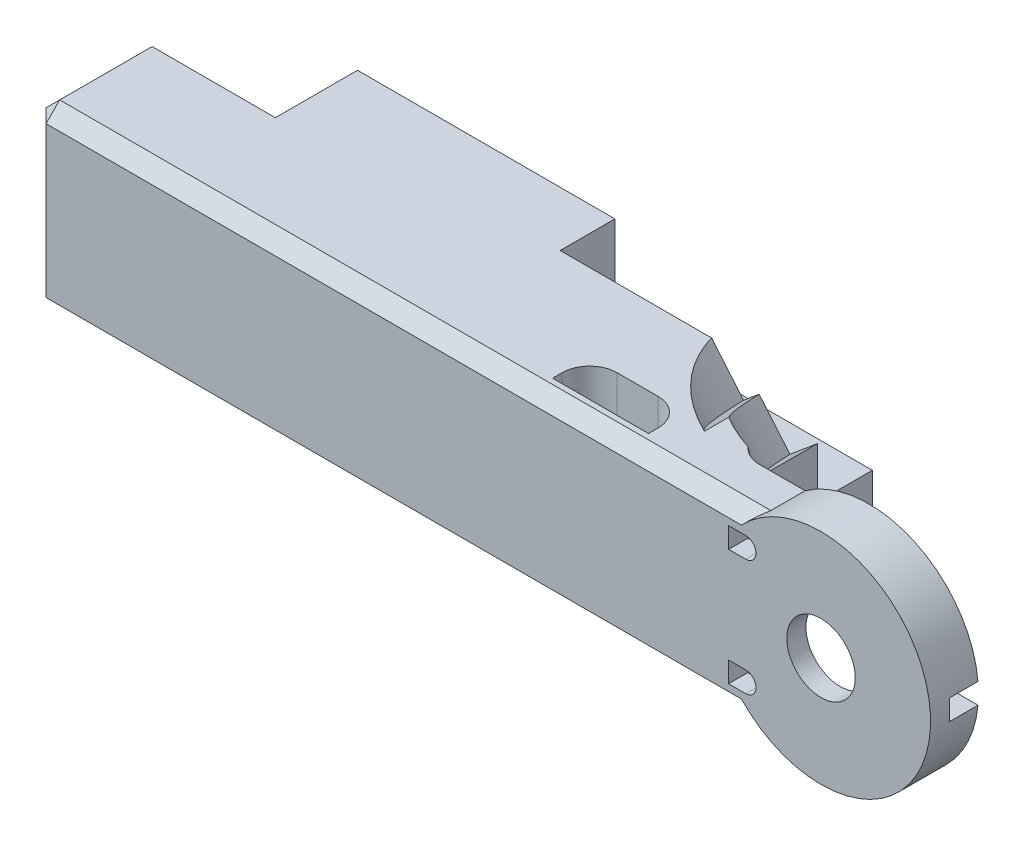
SolidWorks part; units mm, degrees
ref_plane "Front Plane" through (0, 0, 0) normal (0, 0, 1) x (1, 0, 0)
ref_plane "Top Plane" through (0, 0, 0) normal (0, 1, 0) x (1, 0, 0)
ref_plane "Right Plane" through (0, 0, 0) normal (1, 0, 0) x (0, 0, -1)
sketch "Sketch1" plane through (0, 0, 0) normal (0, 0, 1) x (1, 0, 0)
  line L0 (-1000, 0) -> (49000, 0) construction
  line L1 (-1003.2111, 6.5) -> (48996.7889, 6.5) construction
  line L2 (-1004.8419, -6.5) -> (48995.1581, -6.5) construction
  line L3 (-15, -6.5) -> (-15, 6.5)
  line L4 (-15, 6.5) -> (-4.6637, 6.5)
  line L5 (-15, -6.5) -> (-4.6637, -6.5)
  arc A0 (-4.6637, -6.5) -> (-4.6637, 6.5) centre (0, 0) ccw
  arc A1 (-8, 0) -> (-4.6637, -6.5) centre (0, 0) ccw construction
  arc A2 (-4.6637, 6.5) -> (-8, 0) centre (0, 0) ccw construction
  point P12 (-15, 0)
  dimension "D1" = 16
  dimension "D2" = 13
  dimension "D3" = 15
extrude "Boss-Extrude1" add sketch "Sketch1" along normal blind 3.5
sketch "Sketch2" plane through (0, 0, 0) normal (0, 0, -1) x (-1, 0, 0)
  line L0 (-1000, 0) -> (49000, 0) construction
  line L1 (0, -1000) -> (0, 49000) construction
  line L3 (-5.75, -1008.4841) -> (-5.75, -0.75) construction
  line L4 (-998.5902, -5.75) -> (49001.4098, -5.75) construction
  line L5 (-997.2865, 5.75) -> (49002.7135, 5.75) construction
  line L6 (-5.75, -0.75) -> (-7.9648, -0.75)
  line L7 (-5.75, 0.75) -> (-7.9648, 0.75)
  line L8 (-5.75, -2.5) -> (-5.75, -0.75)
  line L9 (-5.75, -2.5) -> (-2.5, -5.75)
  line L10 (-5.75, 2.5) -> (-2.5, 5.75)
  line L11 (-2.5, -5.75) -> (6.75, -5.75)
  line L12 (-2.5, 5.75) -> (6.75, 5.75)
  line L13 (6.75, -1004.2518) -> (6.75, 48995.7482) construction
  line L15 (6.75, -5.75) -> (6.75, 5.75)
  line L16 (-5.75, 0) -> (-5.75, 0.75) construction
  line L17 (-5.75, 0.75) -> (-5.75, 2.5)
  line L18 (-5.75, 0) -> (-5.75, 0.75) construction
  line L19 (-5.75, 0.75) -> (-5.75, 48991.5159) construction
  line L20 (-5.75, -0.75) -> (-5.75, 0) construction
  line L21 (-5.75, -0.75) -> (-5.75, 0) construction
  line L22 (-2.5, -1002.5522) -> (-2.5, 48997.4478) construction
  arc A0 (-7.9648, -0.75) -> (-7.9648, 0.75) centre (0, 0) cw
  circle A1 centre (0, 0) radius 8 construction
  point P25 (-5.5, 0)
  dimension "D6" = 8
  dimension "D1" = 5.75
  dimension "D2" = 5.75
  dimension "D3" = 5.75
  dimension "D4" = 0.75
  dimension "D5" = 0.75
  dimension "D7" = 5
  dimension "D8" = 45
  dimension "D9" = 45
  dimension "D10" = 2.5
  dimension "D11" = 6.75
extrude "Cut-Extrude1" cut sketch "Sketch2" against normal blind 2.1
sketch "Sketch3" plane through (0, 0, 2.1) normal (0, 0, -1) x (-1, 0, 0)
  line L0 (5.5, -5) -> (6.75, -5)
  line L1 (5.5, -3.5) -> (6.75, -3.5)
  line L2 (5.5, 3.5) -> (6.75, 3.5)
  line L3 (5.5, 5) -> (6.75, 5)
  line L5 (6.75, -5.75) -> (6.75, 5.75) construction
  line L7 (6.75, 5) -> (6.75, 3.5)
  line L9 (6.75, -3.5) -> (6.75, -5)
  circle A0 centre (0, 0) radius 2.5
  arc A1 (5.5, -3.5) -> (5.5, -5) centre (5.5, -4.25) ccw
  arc A2 (5.5, 5) -> (5.5, 3.5) centre (5.5, 4.25) ccw
  arc A6 (5.5, -5) -> (5.5, -3.5) centre (5.5, -4.25) ccw construction
  arc A7 (5.5, 3.5) -> (5.5, 5) centre (5.5, 4.25) ccw construction
  dimension "D1" = 5
  dimension "D2" = 1.5
  dimension "D3" = 1.5
extrude "Cut-Extrude2" cut sketch "Sketch3" against normal through all
sketch "Sketch5" plane through (0, 0, 3.5) normal (0, 0, -1) x (-1, 0, 0)
  line L1 (15, -6.5) -> (10, -6.5)
  line L2 (15, -6.5) -> (15, 6.5)
  line L3 (15, 6.5) -> (10, 6.5)
  line L4 (10, -6.5) -> (10, 6.5)
  line L5 (15, -6.5) -> (4.6637, -6.5) construction
  line L6 (4.6637, 6.5) -> (15, 6.5) construction
  line L7 (15, 6.5) -> (15, -6.5) construction
  dimension "D1" = 10
extrude "Boss-Extrude3" add sketch "Sketch5" along normal blind 11.75
ref_plane "Plane1" through (-57.6, 0, 0) normal (1, 0, 0) x (0, 0, -1)
sketch "Sketch6" plane through (-15, 0, 0) normal (-1, 0, 0) x (0, 0, 1)
  line L1 (-8.25, 6.5) -> (3.5, 6.5)
  line L2 (-8.25, 6.5) -> (-8.25, -6.5)
  line L3 (-8.25, -6.5) -> (3.5, -6.5)
  line L4 (3.5, 6.5) -> (3.5, -6.5)
extrude "Boss-Extrude4" add sketch "Sketch6" along normal up to surface (42.6 mm away) up to plane "Plane1"
sketch "Sketch7" plane through (0, 0, -8.25) normal (0, 0, -1) x (-1, 0, 0)
  line L0 (10, -6.5) -> (57.6, -6.5) construction
  line L1 (57.6, 6.5) -> (47.6, 6.5)
  line L2 (57.6, 6.5) -> (57.6, -6.5)
  line L3 (57.6, -6.5) -> (47.6, -6.5)
  line L4 (47.6, 6.5) -> (47.6, -6.5)
  dimension "D1" = 10
extrude "Cut-Extrude3" cut sketch "Sketch7" against normal blind 4
chamfer "Chamfer1" distance 1 angle 45 5 edges at (-57.6, -6.5, -0.375) (-57.6, 0, 3.5) (-57.6, 6.5, -0.375) (-31.1318, -6.5, 3.5) (-31.1318, 6.5, 3.5)
sketch "Sketch17" plane through (0, 0, -8.25) normal (0, 0, -1) x (-1, 0, 0)
  line L0 (47.6, 6.5) -> (28.8, 6.5)
  line L3 (47.6, 6.5) -> (10, 6.5) construction
  line L6 (28.8, 6.5) -> (28.8, 0.5)
  line L23 (10, -6.5) -> (47.6, -6.5) construction
  line L24 (28.8, -6.5) -> (10, -6.5)
  line L25 (10, -6.5) -> (10, 0)
  line L26 (10, 6.5) -> (10, -6.5) construction
  line L27 (10, 0) -> (28.3, 0)
  line L28 (47.6, 6.5) -> (47.6, -6.5) construction
  line L29 (47.6, 0) -> (47.6, 6.5)
  line L30 (28.8, 0.5) -> (29.3, 0)
  line L31 (28.3, 0) -> (28.8, -0.5)
  line L32 (28.8, 0) -> (28.8, -0.5) construction
  line L33 (28.8, -0.5) -> (28.8, -6.5)
  line L34 (28.8, 0) -> (29.3, 0) construction
  line L35 (29.3, 0) -> (47.6, 0)
  line L36 (28.8, 0.5) -> (28.8, 0) construction
  line L37 (28.3, 0) -> (28.8, 0) construction
  circle A2 centre (28.8, 0) radius 0.5 construction
  dimension "D1" = 1
sketch "Sketch19" plane through (-6.75, 0, 0) normal (1, 0, 0) x (0, 0, -1)
  line L1 (-2.1, 4.5) -> (0.6, 4.5)
  line L2 (-2.1, 4.5) -> (-2.1, -4.5)
  line L3 (-2.1, -4.5) -> (0.6, -4.5)
  line L4 (0.6, 4.5) -> (0.6, -4.5)
  line L9 (-2.1, -3.5) -> (-2.1, 3.5) construction
  point P4 (0.6, 0)
  dimension "D1" = 2.7
  dimension "D2" = 9
extrude "Cut-Extrude10" cut sketch "Sketch19" against normal blind 14.25
sketch "Sketch20" plane through (0, 4.5, 0) normal (0, -1, 0) x (1, 0, 0)
  line L0 (-21, -0.6) -> (-10, -0.6) construction
  line L1 (-21, 2.1) -> (-14, 2.1)
  line L2 (-21, 2.1) -> (-21, -0.6)
  line L3 (-21, -0.6) -> (-14, -0.6)
  line L4 (-14, 2.1) -> (-14, -0.6)
  dimension "D1" = 7
extrude "Cut-Extrude11" cut sketch "Sketch20" against normal through all
fillet "Fillet4" radius 3 2 edges at (-12, 4.5, -0.6) (-15.5, -4.5, -0.6)
sketch "Sketch23" plane through (0, 0, 0) normal (0, 0, -1) x (-1, 0, 0)
  line L0 (6.75, 4.5) -> (10, 4.5)
  line L1 (6.75, 3.315) -> (6.75, 5.75) construction
  line L2 (10, 6.5) -> (10, 3.315) construction
  line L3 (10, 4.5) -> (10, -4.5)
  line L4 (10, -4.5) -> (6.75, -4.5)
  line L5 (6.75, -5.75) -> (6.75, -3.315) construction
  line L6 (6.75, -4.5) -> (6.75, 4.5)
  line L7 (14, 4.5) -> (6.75, 4.5) construction
  line L8 (21, -4.5) -> (6.75, -4.5) construction
extrude "Cut-Extrude14" cut sketch "Sketch23" against normal up to surface (2.1 mm away) and the other way through all up to face at (-2.5, 0, 2.1)
fillet "Fillet5" radius 2 8 edges at (-21, -3.5275, 0.1751) (-14, 4.0075, -0.6) (-21, 2.4925, -0.6) (-10, -5.5, 0) (-10, 5.5, 0) (-10, -4.5, 1.05) (-10, 4.5, 1.05) (-14, 3.5275, 0.1751)
extrude "Boss-Extrude7" add sketch "Sketch17" along normal blind 2
sketch "Sketch21" plane through (0, 0, -8.25) normal (0, 0, -1) x (-1, 0, 0)
  line L0 (10, 6.5) -> (10, 0)
  line L1 (10, 0) -> (28.3, 0)
  line L2 (28.3, 0) -> (28.8, -0.5)
  line L3 (28.8, -0.5) -> (28.8, -6.5)
  line L4 (28.8, -6.5) -> (47.6, -6.5)
  line L5 (47.6, -6.5) -> (47.6, 0)
  line L6 (47.6, 0) -> (29.3, 0)
  line L7 (29.3, 0) -> (28.8, 0.5)
  line L8 (28.8, 0.5) -> (28.8, 6.5)
  line L9 (28.8, 6.5) -> (10, 6.5)
extrude "Cut-Extrude12" cut sketch "Sketch21" against normal blind 2
sketch "Sketch22" plane through (-57.6, 0, 0) normal (-1, 0, 0) x (0, 0, 1)
  line L0 (-2.125, -5.5) -> (-2.125, 5.5) construction
  line L1 (-4.25, -5.5) -> (2.5, -5.5) construction
  line L2 (2.5, 5.5) -> (-4.25, 5.5) construction
  line L3 (-4.25, -5.5) -> (-4.25, 5.5) construction
  arc A0 (-2.125, -1.625) -> (-2.125, -0.475) centre (-2.125, -1.05) ccw
  arc A1 (-2.125, 0.475) -> (-2.125, 1.625) centre (-2.125, 1.05) ccw
  arc A2 (-2.125, -0.475) -> (-2.125, -1.625) centre (-2.125, -1.05) ccw construction
  arc A3 (-2.125, 1.625) -> (-2.125, 0.475) centre (-2.125, 1.05) ccw construction
  ellipse E0 centre (-2.125, -1.05) end of major axis (-2.875, -1.05) minor radius 0.575 (-2.125, -0.475) -> (-2.125, -1.625) ccw
  ellipse E1 centre (-2.125, 1.05) end of major axis (-1.375, 1.05) minor radius 0.575 (-2.125, 1.625) -> (-2.125, 0.475) ccw
  ellipse E2 centre (-2.125, -1.05) end of major axis (-2.875, -1.05) minor radius 0.575 (-2.125, -1.625) -> (-2.125, -0.475) ccw construction
  ellipse E3 centre (-2.125, 1.05) end of major axis (-1.375, 1.05) minor radius 0.575 (-2.125, 0.475) -> (-2.125, 1.625) ccw construction
  point P10 (-2.125, 0)
  dimension "D2" = 1.15
  dimension "D3" = 1.15
  dimension "D1" = 1.05
  dimension "D4" = 2.1
  dimension "D5" = 2.125
  dimension "D6" = 0.75
  dimension "D7" = 0.75
extrude "Cut-Extrude13" cut sketch "Sketch22" against normal through all
fillet "Fillet6" radius 0.25 8 edges at (-57.6, 1.05, -1.55) (-57.6, -1.05, -1.55) (-10, 1.05, -1.55) (-10, -1.05, -1.55) (-10, 1.05, -2.875) (-57.6, 1.05, -2.875) (-10, -1.05, -2.875) (-57.6, -1.05, -2.875)
ref_plane "Plane2" through (0, 0, -8.25) normal (0, 0, 1) x (1, 0, 0)
sketch "Sketch25" plane through (0, 0, -8.25) normal (0, 0, 1) x (1, 0, 0)
  line L0 (-18.0119, 6.5) -> (-6.6551, 6.5)
  line L2 (-5.8095, 5.5) -> (-56.6, 5.5) construction
  line L3 (-15.5693, 3.589) -> (-18.0119, 6.5)
  line L4 (-56.6, 6.5) -> (-4.6637, 6.5) construction
  line L6 (-57.6, -5.5) -> (-57.6, 5.5) construction
  line L7 (-15.5693, 3.589) -> (-14.4585, 4.5211)
  line L8 (-14.4585, 4.5211) -> (-12.2088, 1.8399)
  line L9 (-12.2088, 1.8399) -> (-6.6551, 6.5)
  line L15 (-16.3038, 5.5) -> (-10, 5.5) construction
  line L20 (0, 0) -> (-9.2453, 11.0181) construction
  dimension "D1" = 40
  dimension "D2" = 3.8
  dimension "D3" = 0.92
  dimension "D4" = 1.45
  dimension "D5" = 3.5
ref_axis "Axis1" through (0, 0, -8.25) along (-0.6428, 0.766, 0)
revolve "Cut-Revolve1" cut sketch "Sketch25" angle 360 about L20
